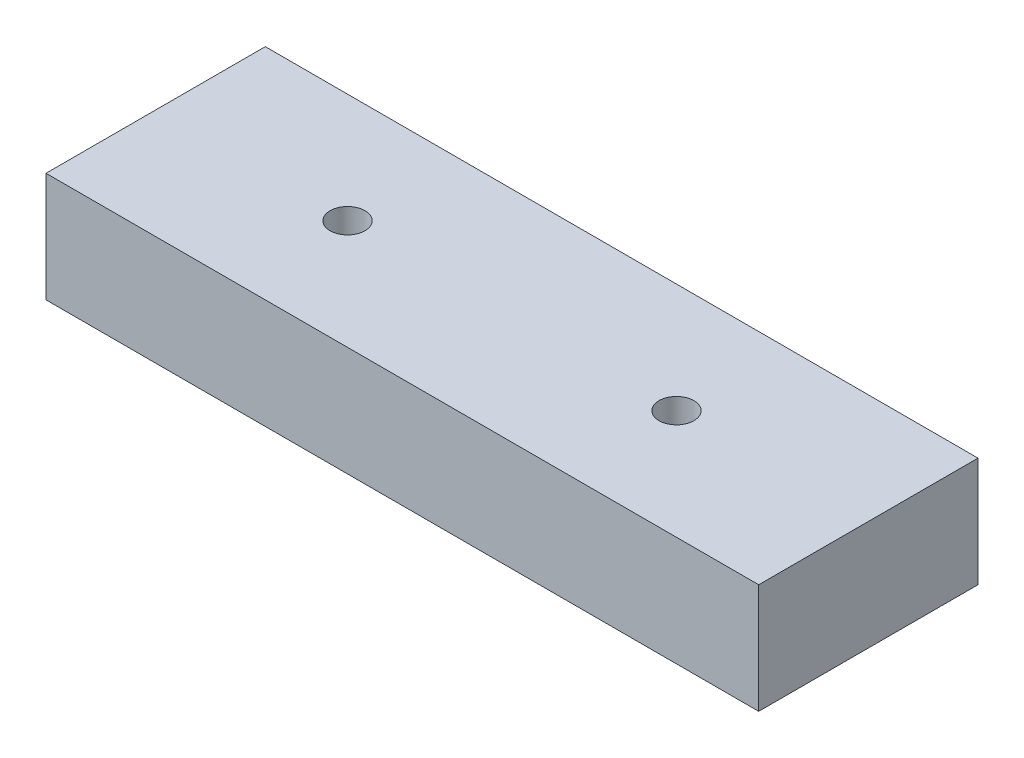
SolidWorks part; units mm, degrees
ref_plane "Front" through (0, 0, 0) normal (0, 0, 1) x (1, 0, 0)
ref_plane "Top" through (0, 0, 0) normal (0, 1, 0) x (1, 0, 0)
ref_plane "Right" through (0, 0, 0) normal (1, 0, 0) x (0, 0, -1)
sketch "Sketch2" plane through (0, 0, 0) normal (0, 1, 0) x (1, 0, 0)
  line L1 (-41.275, -12.7) -> (41.275, -12.7)
  line L2 (-41.275, -12.7) -> (-41.275, 12.7)
  line L3 (-41.275, 12.7) -> (41.275, 12.7)
  line L4 (41.275, -12.7) -> (41.275, 12.7)
  line L5 (-41.275, -12.7) -> (41.275, 12.7) construction
  line L6 (-41.275, 12.7) -> (41.275, -12.7) construction
  point P0 (0, 0)
  dimension "D1" = 82.55
  dimension "D2" = 25.4
extrude "Boss-Extrude1" add sketch "Sketch2" along normal blind 12.7
sketch "Sketch5" plane through (0, 0, 0) normal (0, -1, 0) x (1, 0, 0)
  line L0 (-31.75, 0) -> (-19.05, 0) construction
  line L1 (-31.75, 3.175) -> (-19.05, 3.175)
  line L2 (-31.75, -3.175) -> (-19.05, -3.175)
  line L3 (-41.275, 12.7) -> (41.275, 12.7) construction
  line L5 (-6.35, 0) -> (6.35, 0) construction
  line L6 (-6.35, 3.175) -> (6.35, 3.175)
  line L7 (-6.35, -3.175) -> (6.35, -3.175)
  line L8 (19.05, 0) -> (31.75, 0) construction
  line L9 (19.05, 3.175) -> (31.75, 3.175)
  line L10 (19.05, -3.175) -> (31.75, -3.175)
  arc A0 (-31.75, 3.175) -> (-31.75, -3.175) centre (-31.75, 0) ccw
  arc A1 (-19.05, -3.175) -> (-19.05, 3.175) centre (-19.05, 0) ccw
  arc A2 (-6.35, 3.175) -> (-6.35, -3.175) centre (-6.35, 0) ccw
  arc A3 (6.35, -3.175) -> (6.35, 3.175) centre (6.35, 0) ccw
  arc A4 (19.05, 3.175) -> (19.05, -3.175) centre (19.05, 0) ccw
  arc A5 (31.75, -3.175) -> (31.75, 3.175) centre (31.75, 0) ccw
  point P2 (-25.4, 0)
  point P9 (0, 0)
  point P19 (25.4, 0)
  dimension "D2" = 6.35
  dimension "D1" = 12.7
  dimension "D3" = 12.7
  dimension "D4" = 25.4
  dimension "D5" = 25.4
extrude "Boss-Extrude2" add sketch "Sketch5" along normal blind 3.175
sketch "Sketch8" plane through (0, -3.175, 0) normal (0, -1, 0) x (-1, 0, 0)
  arc A0 (-19.05, -3.175) -> (-19.05, 3.175) centre (-19.05, 0) ccw construction
  arc A1 (19.05, 3.175) -> (19.05, -3.175) centre (19.05, 0) ccw construction
  point P0 (19.05, 0)
  point P2 (-19.05, 0)
  point P11 (-19.05, 0)
hole_wizard "#10-32 Tapped Hole1" positions "Sketch8" profile "Sketch7" tap size "#10-32" standard "ANSI Inch" end condition through all
sketch "Sketch7" plane through (-19.05, -3.175, 0) normal (1, 0, 0) x (0, 0, -1)
  line L0 (0, 0) -> (0, 15.875)
  line L1 (0, 15.875) -> (2.0193, 15.875)
  line L2 (2.0193, 15.875) -> (2.0193, 0)
  line L5 (2.0193, 0) -> (0, 0)
  line L11 (0, -6.35) -> (0, 107.95) construction
  dimension "Thru Tap Drill Dia." = 4.0386
  dimension "Thru Tap Drill Depth" = 15.875
cosmetic thread "Hole Thread1" parameters "D2"=4.826
cosmetic thread "Hole Thread2" parameters "D2"=4.826
